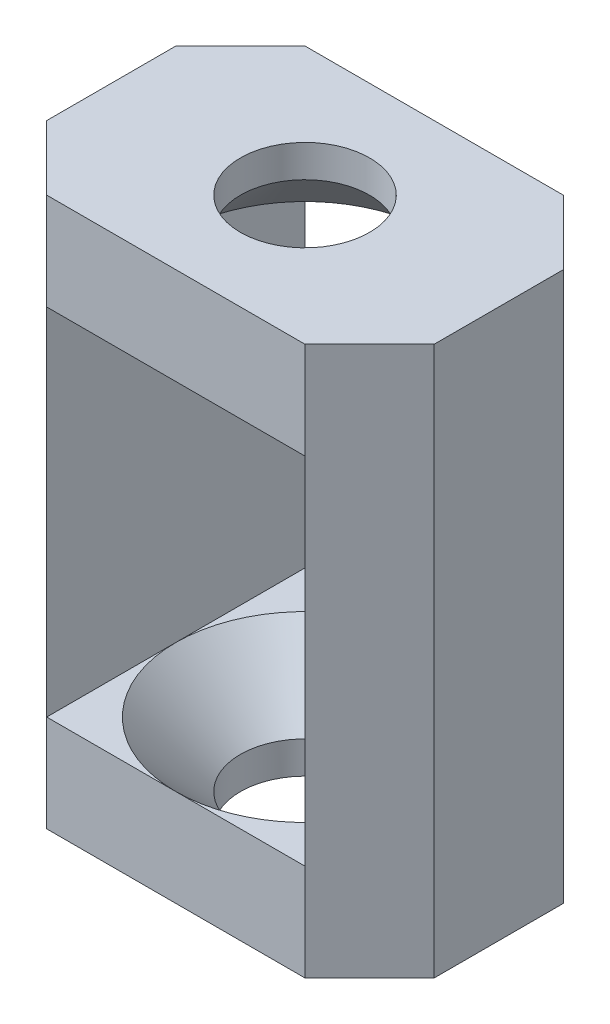
SolidWorks part; units mm, degrees
ref_plane "前视基准面" through (0, 0, 0) normal (0, 0, 1) x (1, 0, 0)
ref_plane "上视基准面" through (0, 0, 0) normal (0, 1, 0) x (1, 0, 0)
ref_plane "右视基准面" through (0, 0, 0) normal (1, 0, 0) x (0, 0, -1)
sketch "草图1" plane through (0, 0, 0) normal (0, 1, 0) x (1, 0, 0)
  line L0 (0, 0) -> (0, 50000) construction
  line L1 (0, 0) -> (50000, 0) construction
  line L3 (-6, -4) -> (6, -4)
  line L4 (-6, -4) -> (-6, 4)
  line L5 (-6, 4) -> (6, 4)
  line L6 (6, -4) -> (6, 4)
  line L7 (-6, -4) -> (6, 4) construction
  line L8 (-6, 4) -> (6, -4) construction
  point P5 (0, 0)
  dimension "D1" = 12
  dimension "D2" = 8
extrude "凸台-拉伸1" add sketch "草图1" along normal blind 17
chamfer "倒角1" distance 2 angle 45 4 edges at (-6, 8.5, -4) (-6, 8.5, 4) (6, 8.5, -4) (6, 8.5, 4)
sketch "草图3" plane through (0, 0, 4) normal (0, 0, 1) x (1, 0, 0)
  line L0 (-6, 0) -> (-6, 17) construction
  line L1 (-4, 14) -> (4, 14)
  line L2 (-4, 14) -> (-4, 3)
  line L3 (-4, 3) -> (4, 3)
  line L4 (4, 14) -> (4, 3)
  line L5 (-4, 14) -> (4, 3) construction
  line L6 (-4, 3) -> (4, 14) construction
  line L7 (0, 8.5) -> (0, 0) construction
  line L8 (-4, 0) -> (4, 0) construction
  line L9 (-4, 17) -> (4, 17) construction
  point P0 (0, 8.5)
  point P11 (-4, 13.7111)
  dimension "D1" = 2
  dimension "D2" = 3
  dimension "D3" = 3
extrude "切除-拉伸1" cut sketch "草图3" against normal mid plane 169
sketch "草图4" plane through (0, 17, 0) normal (0, 1, 0) x (1, 0, 0)
  circle A0 centre (0, 0) radius 2
  dimension "D1" = 4
extrude "切除-拉伸2" cut sketch "草图4" against normal through all both and the other way through all
chamfer "倒角2" distance 2 angle 45 2 edges at (0, 14, 2) (2, 3, 0)
